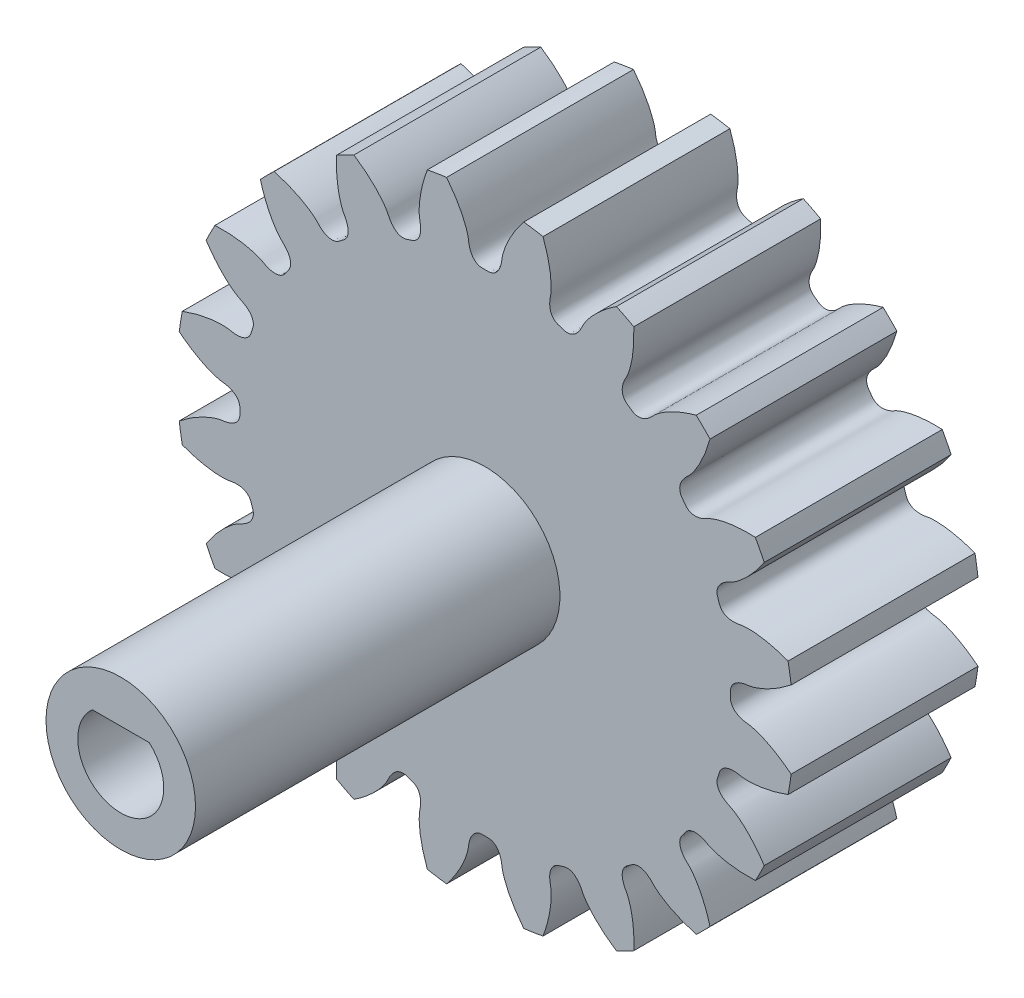
SolidWorks part; units mm, degrees
ref_plane "Front Plane" through (0, 0, 0) normal (0, 0, 1) x (1, 0, 0)
ref_plane "Top Plane" through (0, 0, 0) normal (0, 1, 0) x (1, 0, 0)
ref_plane "Right Plane" through (0, 0, 0) normal (1, 0, 0) x (0, 0, -1)
ref_axis "Axis1" through (0, 0, 55) along (0, 0, -1)
sketch "SketchRevolveSpurAssembly01Pinion" plane through (0, 0, 0) normal (1, 0, 0) x (0, 0, -1)
  line L0 (0, 0) -> (1, 0) construction
  line L1 (-5, 0) -> (-5, 16.5)
  line L2 (-5, 16.5) -> (5, 16.5)
  line L3 (5, 16.5) -> (5, 0)
  line L4 (5, 0) -> (-5, 0)
  dimension "Side1" = 5
  dimension "OutsideRadius" = 16.5
  dimension "Side2" = 5
revolve "SpurAssembly01Pinion" add sketch "SketchRevolveSpurAssembly01Pinion" angle 360 about L0
sketch "SketchToothSpurAssembly01Pinion" plane through (0, 0, 0) normal (0, 0, 1) x (1, 0, 0)
  arc A0 (16.4388, 2.1204) -> (16.4388, -2.1204) centre (0, 0) cw
  spline S0 degree 3 poles (16.4388, -2.1204) (16.3062, -2.0126) (16.1079, -1.8609) (15.8417, -1.6767) (15.6549, -1.5557) (15.4759, -1.4476) (15.3054, -1.3516) (15.1441, -1.2672) (14.9923, -1.1937) (14.8506, -1.1305) (14.7196, -1.0767) (14.5996, -1.0318) (14.491, -0.9949) (14.3942, -0.9653) (14.3096, -0.9423) (14.2375, -0.925) (14.178, -0.9126) (14.0492, -0.8903) (13.9123, -0.8782) (13.7697, -0.8427) (13.6956, -0.8206) (13.6244, -0.795) (13.5557, -0.7654) (13.4893, -0.7311) (13.4248, -0.6913) (13.3623, -0.6446) (13.3021, -0.5892) (13.2452, -0.523) (13.1943, -0.4439) (13.1533, -0.3509) (13.1303, -0.2534) (13.1208, -0.135) (13.1277, 0) (13.1208, 0.135) (13.1303, 0.2534) (13.1533, 0.3509) (13.1943, 0.4439) (13.2452, 0.523) (13.3021, 0.5892) (13.3623, 0.6446) (13.4248, 0.6913) (13.4893, 0.7311) (13.5557, 0.7654) (13.6244, 0.795) (13.6956, 0.8206) (13.7697, 0.8427) (13.9123, 0.8782) (14.0492, 0.8903) (14.178, 0.9126) (14.2375, 0.925) (14.3096, 0.9423) (14.3942, 0.9653) (14.491, 0.9949) (14.5996, 1.0318) (14.7196, 1.0767) (14.8506, 1.1305) (14.9923, 1.1937) (15.1441, 1.2672) (15.3054, 1.3516) (15.4759, 1.4476) (15.6549, 1.5557) (15.8417, 1.6767) (16.1079, 1.8609) (16.3062, 2.0126) (16.4388, 2.1204) knots 0 0 0 0 0.061423 0.08971 0.11638 0.141434 0.164872 0.186693 0.206898 0.225486 0.242459 0.257814 0.271554 0.283677 0.294183 0.303073 0.310347 0.316004 0.350077 0.359568 0.368803 0.377844 0.386769 0.395676 0.404689 0.413963 0.423683 0.434051 0.445256 0.457401 0.47042 0.481067 0.5 0.518933 0.52958 0.542599 0.554744 0.565949 0.576317 0.586037 0.595311 0.604324 0.613231 0.622156 0.631197 0.640432 0.649923 0.683996 0.689653 0.696927 0.705817 0.716323 0.728446 0.742186 0.757541 0.774514 0.793102 0.813307 0.835128 0.858566 0.88362 0.91029 0.938577 1 1 1 1
extrude "ToothExtrudeCutSpurAssembly01Pinion" cut sketch "SketchToothSpurAssembly01Pinion" against normal blind 5 and the other way blind 5
pattern_circular "PatternSpurAssembly01Pinion" count 20 every 18 about axis through (0, 0, 55) along (0, 0, -1) of "ToothExtrudeCutSpurAssembly01Pinion"
sketch "AuxiliarySketchSpurAssembly01Pinion" plane through (0, 0, 0) normal (0, 0, 1) x (1, 0, 0)
  circle A0 centre (0, 0) radius 15 construction
  circle A1 centre (0, 0) radius 14.0954 construction
  circle A2 centre (0, 0) radius 14.1048 construction
  circle A3 centre (0, 0) radius 16.5 construction
  circle A4 centre (0, 0) radius 13.125 construction
  dimension "PitchDiameter" = 30
  dimension "BaseDiameter" = 28.1908
  dimension "FormDiameter" = 28.2095
  dimension "MajorDiameter" = 33
  dimension "MinorDiameter" = 26.25
sketch "Sketch1" plane through (0, 0, 5) normal (0, 0, 1) x (1, 0, 0)
  circle A0 centre (0, 0) radius 4
extrude "Boss-Extrude1" add sketch "Sketch1" along normal blind 19.5
sketch "Sketch7" plane through (0, 0, 24.5) normal (0, 0, 1) x (1, 0, 0)
  line L0 (0, 0) -> (0, 1.725) construction
  line L1 (1.5213, 1.725) -> (-1.5213, 1.725)
  circle A0 centre (0, 0) radius 2.3 construction
  arc A1 (1.5213, 1.725) -> (-1.5213, 1.725) centre (0, 0) cw
  point P10 (0, 1.725)
extrude "Cut-Extrude5" cut sketch "Sketch7" against normal blind 8 contours L1 A1
sketch "Sketch8" plane through (0, 0, -5) normal (0, 0, -1) x (-1, 0, 0)
  circle A0 centre (0, 0) radius 4
extrude "Boss-Extrude5" add sketch "Sketch8" along normal blind 5
